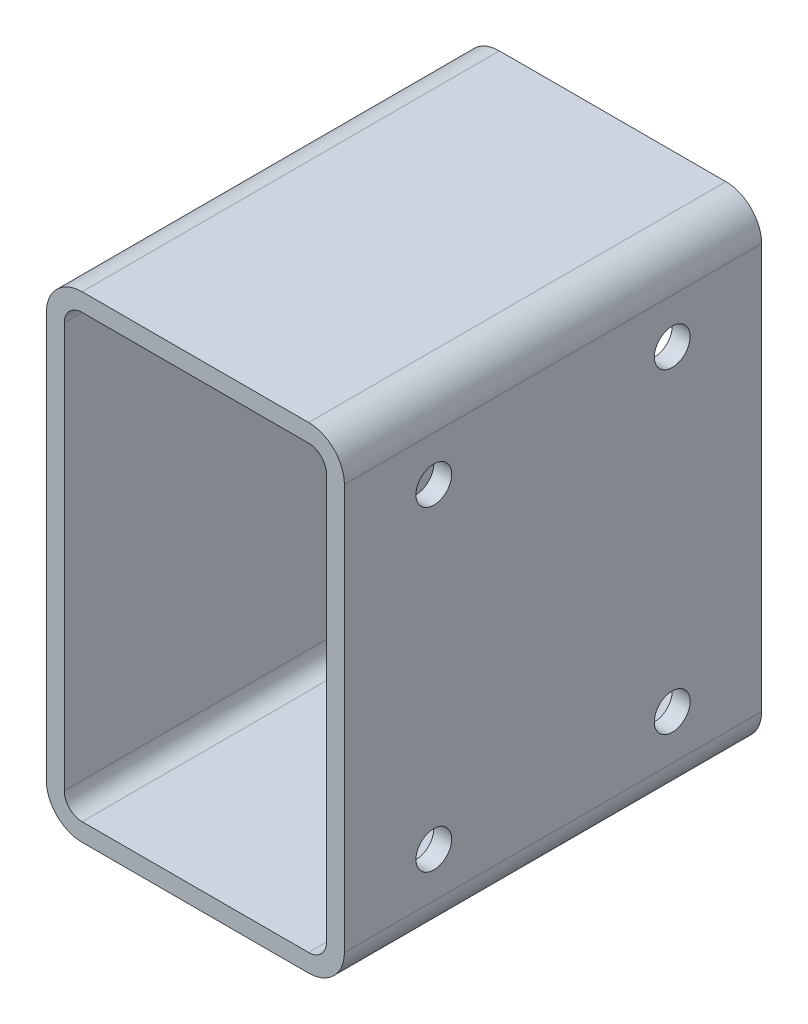
SolidWorks part; units mm, degrees
ref_plane "Front Plane" through (0, 0, 0) normal (0, 0, 1) x (1, 0, 0)
ref_plane "Top Plane" through (0, 0, 0) normal (0, 1, 0) x (1, 0, 0)
ref_plane "Right Plane" through (0, 0, 0) normal (1, 0, 0) x (0, 0, -1)
sketch "Sketch1" plane through (0, 0, 0) normal (0, 0, 1) x (1, 0, 0)
  line L0 (19, 37) -> (-19, 37)
  line L1 (19, -40) -> (-19, -40)
  line L2 (25, -34) -> (25, 34)
  line L3 (19, 40) -> (-19, 40)
  line L4 (-25, -34) -> (-25, 34)
  line L5 (25, -40) -> (-25, 40) construction
  line L6 (25, 40) -> (-25, -40) construction
  line L7 (-22, -34) -> (-22, 34)
  line L8 (19, -37) -> (-19, -37)
  line L9 (22, -34) -> (22, 34)
  arc A0 (-19, -40) -> (-25, -34) centre (-19, -34) cw
  arc A1 (19, -40) -> (25, -34) centre (19, -34) ccw
  arc A2 (25, 34) -> (19, 40) centre (19, 34) ccw
  arc A3 (-19, 40) -> (-25, 34) centre (-19, 34) ccw
  arc A4 (-19, 37) -> (-22, 34) centre (-19, 34) ccw
  arc A5 (-19, -37) -> (-22, -34) centre (-19, -34) cw
  arc A6 (19, -37) -> (22, -34) centre (19, -34) ccw
  arc A7 (22, 34) -> (19, 37) centre (19, 34) ccw
  point P0 (0, 0)
  dimension "D1" = 6
  dimension "D3" = 80
  dimension "D4" = 50
  dimension "D2" = 3
extrude "Boss-Extrude1" add sketch "Sketch1" along normal mid plane 70
sketch "Sketch2" plane through (25, 0, 0) normal (1, 0, 0) x (0, 0, -1)
  line L1 (20, -26.5) -> (-20, -26.5) construction
  line L2 (20, -26.5) -> (20, 26.5) construction
  line L3 (20, 26.5) -> (-20, 26.5) construction
  line L4 (-20, -26.5) -> (-20, 26.5) construction
  line L5 (20, -26.5) -> (-20, 26.5) construction
  line L6 (20, 26.5) -> (-20, -26.5) construction
  circle A0 centre (-20, 26.5) radius 3
  circle A1 centre (20, 26.5) radius 3
  circle A2 centre (20, -26.5) radius 3
  circle A3 centre (-20, -26.5) radius 3
  point P0 (0, 0)
  dimension "D3" = 6
  dimension "D1" = 40
  dimension "D2" = 53
extrude "Cut-Extrude1" cut sketch "Sketch2" against normal blind 10
equation "\"M5_tap\"=4.2mm       ' Below you can do mesurements as follows: cm, mm, ft, in, m, "
equation "\"M5_clearence\"=5.5mm"
equation "\"M6_tap\"=5mm"
equation "\"M6_clearence\"=6.6mm"
equation "\"work_area_width\"=1100mm"
equation "\"work_area_depth\"=900mm"
equation "\"D3@Sketch1\"=\"steel_rollers_width\""
equation "\"D4@Sketch1\"=\"steel_rollers_height\""
equation "\"D1@Sketch1\"=\"steel_rollers_radius\""
equation "\"D2@Sketch1\"=\"steel_rollers_wall_thickness\""
equation "\"D1@Boss-Extrude1\"=\"work_area_depth\" + 200"
equation "\"steel_base_width\"=80mm"
equation "\"steel_base_height\"=50mm"
equation "\"steel_base_wall_thickness\"=3mm"
equation "\"steel_base_radius\"=6mm"
equation "\"steel_sides_width\"=80mm    'this tube is rotated so flip width/height"
equation "\"steel_sides_height\"=50mm    'this tube is rotated so flip width/height"
equation "\"steel_sides_wall_thickness\"=3mm"
equation "\"steel_sides_radius\"=6mm"
equation "\"steel_gantry_width\"=80mm    'this tube is rotated so flip width/height"
equation "\"steel_gantry_height\"=50mm    'this tube is rotated so flip width/height"
equation "\"steel_gantry_wall_thickness\"=3mm"
equation "\"steel_gantry_radius\"=6mm"
equation "\"steel_rollers_width\"=80mm"
equation "\"steel_rollers_height\"=50mm    'keep as low as possible as this increases how big plastic parts are"
equation "\"steel_rollers_wall_thickness\"=3mm"
equation "\"steel_rollers_radius\"=6mm"
equation "\"steel_zbox_width\"=80mm     'if the gantry height (rotated) is too thick, a wider zbox is necessary"
equation "\"steel_zbox_height\"=50mm    'hole patteren changes as the zbox and gantry height (rotated) changes."
equation "\"steel_zbox_wall_thickness\"=3mm"
equation "\"steel_zbox_radius\"=6mm"
